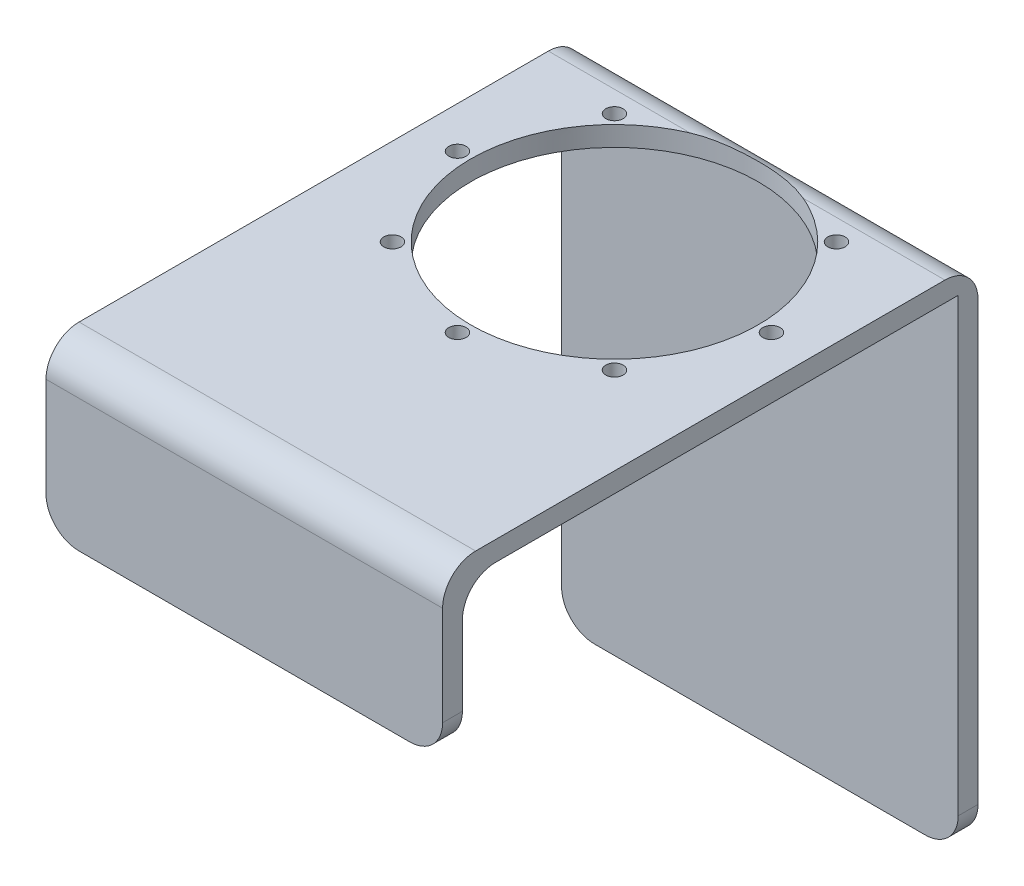
SolidWorks part; units mm, degrees
ref_plane "Alzado" through (0, 0, 0) normal (0, 0, 1) x (1, 0, 0)
ref_plane "Planta" through (0, 0, 0) normal (0, 1, 0) x (1, 0, 0)
ref_plane "Vista lateral" through (0, 0, 0) normal (1, 0, 0) x (0, 0, -1)
sketch "Croquis1" plane through (0, 0, 0) normal (0, 0, 1) x (1, 0, 0)
  line L8 (-112.102, -77.1) -> (7.898, -77.1)
  line L9 (-112.102, -77.1) -> (-112.102, -229.5)
  line L10 (-112.102, -229.5) -> (7.898, -229.5)
  line L11 (7.898, -77.1) -> (7.898, -229.5)
  line L12 (7.898, -77.1) -> (7.898, -229.5) construction
  line L13 (-112.102, -77.1) -> (7.898, -77.1) construction
  point P5 (-52.102, -229.5)
  dimension "D1" = 120
extrude "Saliente-Extruir1" add sketch "Croquis1" along normal blind 6
sketch "Croquis2" plane through (0, 0, 6) normal (0, 0, 1) x (1, 0, 0)
  line L5 (-112.102, -77.1) -> (-112.102, -229.5) construction
  line L6 (-112.102, -83.1) -> (7.898, -83.1)
  line L7 (-112.102, -83.1) -> (-112.102, -77.1)
  line L8 (-112.102, -77.1) -> (7.898, -77.1)
  line L9 (7.898, -83.1) -> (7.898, -77.1)
  dimension "D1" = 6
extrude "Saliente-Extruir2" add sketch "Croquis2" along normal up to surface (156 mm away)
sketch "Croquis3" plane through (0, 0, 162) normal (0, 0, 1) x (1, 0, 0)
  line L0 (7.898, -229.5) -> (7.898, -83.1) construction
  line L5 (-112.102, -83.1) -> (7.898, -83.1)
  line L6 (-112.102, -83.1) -> (-112.102, -127.1)
  line L7 (-112.102, -127.1) -> (7.898, -127.1)
  line L16 (7.898, -83.1) -> (7.898, -127.1)
  line L17 (7.898, -77.1) -> (-112.102, -77.1) construction
  dimension "50" = 50
extrude "Saliente-Extruir3" add sketch "Croquis3" against normal blind 6
fillet "Redondeo1" radius 10 7 edges at (-52.102, -83.1, 156) (-52.102, -77.1, 162) (-52.102, -77.1, 0) (-112.102, -229.5, 3) (7.898, -229.5, 3) (-112.102, -127.1, 159) (7.898, -127.1, 159)
sketch "Croquis4" plane through (0, -83.1, 0) normal (0, -1, 0) x (1, 0, 0)
  circle A2 centre (-85.6896, 16.4124) radius 2.621
  circle A3 centre (-18.5145, 83.5876) radius 2.621
  circle A4 centre (-18.5145, 83.5876) radius 2.621
  circle A5 centre (-85.6896, 16.4124) radius 2.621
  circle A6 centre (-4.602, 50) radius 2.621
  circle A7 centre (-4.602, 50) radius 2.621
  circle A9 centre (-18.5145, 16.4124) radius 2.621
  circle A10 centre (-18.5145, 16.4124) radius 2.621
  circle A12 centre (-85.6896, 83.5876) radius 2.621
  circle A13 centre (-85.6896, 83.5876) radius 2.621
  circle A15 centre (-99.602, 50) radius 2.621
  circle A16 centre (-52.102, 97.5) radius 2.621
  circle A17 centre (-52.102, 97.5) radius 2.621
  circle A18 centre (-99.602, 50) radius 2.621
  spline S0 degree 3 poles (-56.0819, 6.6207) (-52.1019, 6.4397) (-48.122, 6.6207) (-44.0966, 7.1778) (-40.0626, 8.1272) (-36.0093, 9.5102) (-32.0574, 11.3088) (-28.2311, 13.545) (-24.6252, 16.1753) (-21.2886, 19.1868) (-18.2772, 22.5233) (-15.6469, 26.1294) (-13.4107, 29.9556) (-11.6121, 33.9076) (-10.2292, 37.9607) (-9.2798, 41.9949) (-8.7227, 46.0201) (-8.5417, 50.0002) (-8.7227, 53.98) (-9.2799, 58.0055) (-10.2293, 62.0395) (-11.6122, 66.0927) (-13.4108, 70.0446) (-15.647, 73.8709) (-18.2774, 77.4768) (-21.2888, 80.8135) (-24.6253, 83.8248) (-28.2314, 86.4552) (-32.0576, 88.6913) (-36.0096, 90.4899) (-40.0627, 91.8728) (-44.0969, 92.8222) (-48.1222, 93.3793) (-52.1022, 93.5603) (-56.0821, 93.3793) (-60.1075, 92.8222) (-64.1415, 91.8727) (-68.1948, 90.4898) (-72.1466, 88.6912) (-75.973, 86.455) (-79.5789, 83.8247) (-82.9155, 80.8132) (-85.9268, 77.4767) (-88.5572, 73.8706) (-90.7934, 70.0444) (-92.592, 66.0924) (-93.9748, 62.0393) (-94.9243, 58.0051) (-95.4813, 53.9799) (-95.6624, 49.9998) (-95.4813, 46.02) (-94.9242, 41.9945) (-93.9748, 37.9605) (-92.5918, 33.9073) (-90.7933, 29.9554) (-88.557, 26.1291) (-85.9267, 22.5232) (-82.9153, 19.1865) (-79.5787, 16.1752) (-75.9727, 13.5448) (-72.1465, 11.3087) (-68.1944, 9.5101) (-64.1414, 8.1272) (-60.1072, 7.1778) (-56.0819, 6.6207) (-52.1019, 6.4397) (-48.122, 6.6207) knots -0.04456 -0.029124 -0.014562 0 0.014563 0.029124 0.044561 0.059997 0.076078 0.092156 0.108579 0.125 0.141423 0.157844 0.173924 0.190003 0.20544 0.220876 0.235439 0.25 0.264563 0.279124 0.294561 0.309997 0.326078 0.342156 0.358579 0.375 0.391423 0.407844 0.423924 0.440003 0.45544 0.470876 0.485439 0.5 0.514563 0.529124 0.544561 0.559997 0.576078 0.592156 0.608579 0.625 0.641423 0.657844 0.673924 0.690003 0.70544 0.720876 0.735439 0.75 0.764563 0.779124 0.794561 0.809997 0.826078 0.842156 0.858579 0.875 0.891423 0.907844 0.923924 0.940003 0.95544 0.970876 0.985438 1 1.014563 1.029124 1.044561 only from (-52.102, 6.5) to (-52.102, 6.5) construction
  spline S1 degree 3 poles (-56.0819, 6.6207) (-52.1019, 6.4397) (-48.122, 6.6207) (-44.0966, 7.1778) (-40.0626, 8.1272) (-36.0093, 9.5102) (-32.0574, 11.3088) (-28.2311, 13.545) (-24.6252, 16.1753) (-21.2886, 19.1868) (-18.2772, 22.5233) (-15.6469, 26.1294) (-13.4107, 29.9556) (-11.6121, 33.9076) (-10.2292, 37.9607) (-9.2798, 41.9949) (-8.7227, 46.0201) (-8.5417, 50.0002) (-8.7227, 53.98) (-9.2799, 58.0055) (-10.2293, 62.0395) (-11.6122, 66.0927) (-13.4108, 70.0446) (-15.647, 73.8709) (-18.2774, 77.4768) (-21.2888, 80.8135) (-24.6253, 83.8248) (-28.2314, 86.4552) (-32.0576, 88.6913) (-36.0096, 90.4899) (-40.0627, 91.8728) (-44.0969, 92.8222) (-48.1222, 93.3793) (-52.1022, 93.5603) (-56.0821, 93.3793) (-60.1075, 92.8222) (-64.1415, 91.8727) (-68.1948, 90.4898) (-72.1466, 88.6912) (-75.973, 86.455) (-79.5789, 83.8247) (-82.9155, 80.8132) (-85.9268, 77.4767) (-88.5572, 73.8706) (-90.7934, 70.0444) (-92.592, 66.0924) (-93.9748, 62.0393) (-94.9243, 58.0051) (-95.4813, 53.9799) (-95.6624, 49.9998) (-95.4813, 46.02) (-94.9242, 41.9945) (-93.9748, 37.9605) (-92.5918, 33.9073) (-90.7933, 29.9554) (-88.557, 26.1291) (-85.9267, 22.5232) (-82.9153, 19.1865) (-79.5787, 16.1752) (-75.9727, 13.5448) (-72.1465, 11.3087) (-68.1944, 9.5101) (-64.1414, 8.1272) (-60.1072, 7.1778) (-56.0819, 6.6207) (-52.1019, 6.4397) (-48.122, 6.6207) knots -0.04456 -0.029124 -0.014562 0 0.014563 0.029124 0.044561 0.059997 0.076078 0.092156 0.108579 0.125 0.141423 0.157844 0.173924 0.190003 0.20544 0.220876 0.235439 0.25 0.264563 0.279124 0.294561 0.309997 0.326078 0.342156 0.358579 0.375 0.391423 0.407844 0.423924 0.440003 0.45544 0.470876 0.485439 0.5 0.514563 0.529124 0.544561 0.559997 0.576078 0.592156 0.608579 0.625 0.641423 0.657844 0.673924 0.690003 0.70544 0.720876 0.735439 0.75 0.764563 0.779124 0.794561 0.809997 0.826078 0.842156 0.858579 0.875 0.891423 0.907844 0.923924 0.940003 0.95544 0.970876 0.985438 1 1.014563 1.029124 1.044561 only from (-52.102, 6.5) to (-52.102, 6.5)
  dimension "D1" = 1
  dimension "D2" = 1
  dimension "D3" = 1
  dimension "D4" = 1
  dimension "D5" = 1
  dimension "D6" = 1
  dimension "D7" = 1
extrude "Cortar-Extruir1" cut sketch "Croquis4" against normal through all
